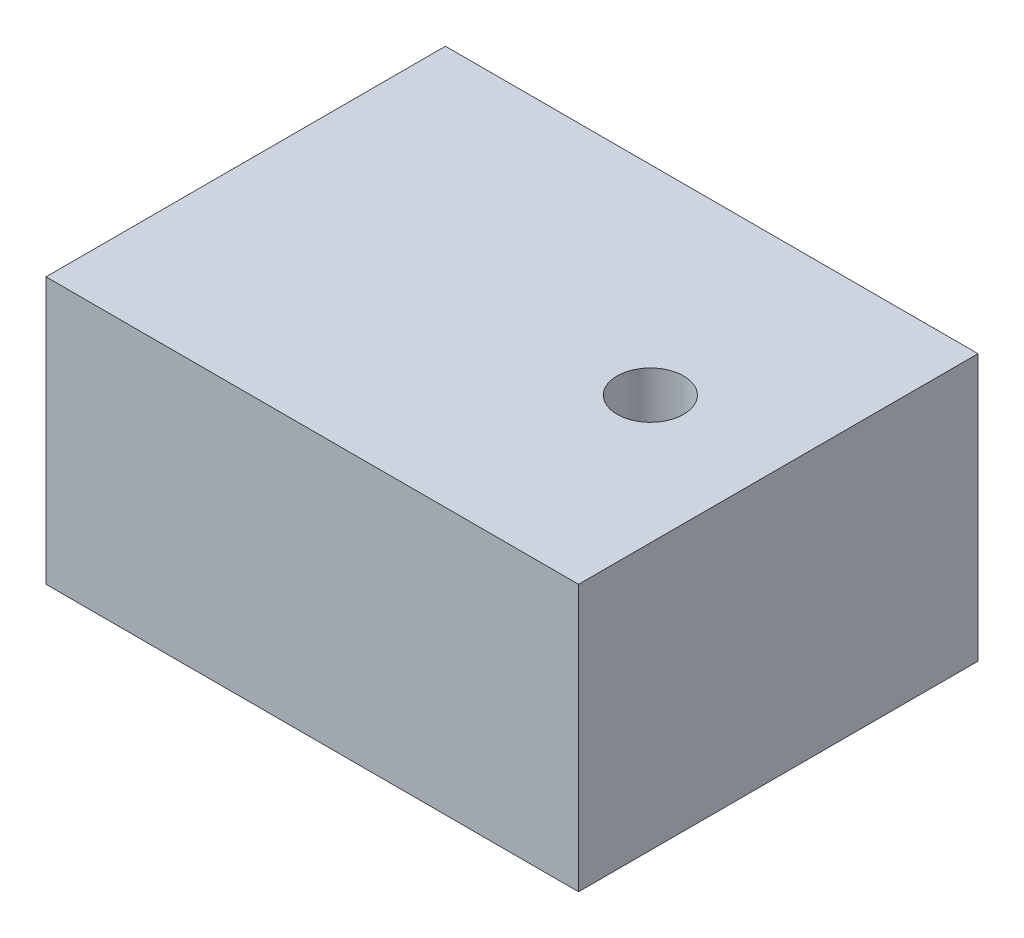
SolidWorks part; units mm, degrees
ref_plane "Front Plane" through (0, 0, 0) normal (0, 0, 1) x (1, 0, 0)
ref_plane "Top Plane" through (0, 0, 0) normal (0, 1, 0) x (1, 0, 0)
ref_plane "Right Plane" through (0, 0, 0) normal (1, 0, 0) x (0, 0, -1)
sketch "Sketch1" plane through (0, 0, 0) normal (0, 1, 0) x (1, 0, 0)
  line L1 (0, 0) -> (50.8, 0)
  line L2 (0, 0) -> (0, 38.1)
  line L3 (0, 38.1) -> (50.8, 38.1)
  line L4 (50.8, 0) -> (50.8, 38.1)
  dimension "D1" = 38.1
  dimension "D2" = 50.8
extrude "Boss-Extrude1" add sketch "Sketch1" along normal blind 25.4
sketch "Sketch2" plane through (0, 25.4, 0) normal (0, 1, 0) x (1, 0, 0)
  line L0 (50.8, 0) -> (50.8, 38.1) construction
  circle A0 centre (38.5966, 19.05) radius 3.175
  point P4 (50.8, 19.05)
  dimension "D1" = 6.35
extrude "Cut-Extrude1" cut sketch "Sketch2" against normal through all
sketch "Sketch3" plane through (0, 0, 0) normal (-1, 0, 0) x (0, 0, 1)
  line L0 (-38.1, 25.4) -> (-38.1, 0) construction
  line L1 (-38.1, 25.4) -> (0, 25.4) construction
  circle A0 centre (-19.05, 12.7) radius 4.7625
  point P4 (-38.1, 12.7)
  point P7 (-19.05, 25.4)
  dimension "D1" = 9.525
extrude "Cut-Extrude2" cut sketch "Sketch3" against normal blind 19.05
